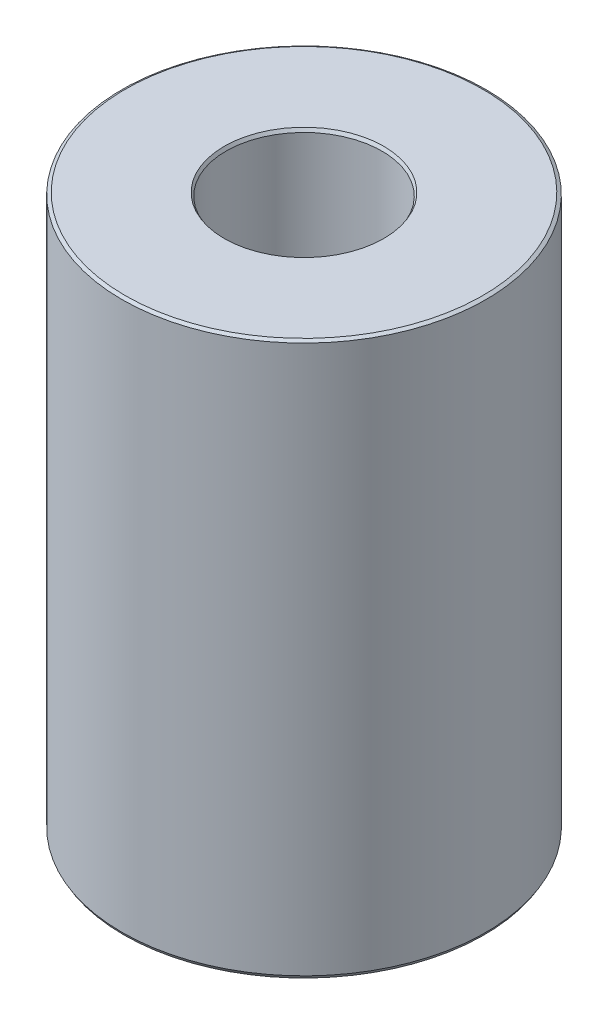
SolidWorks part; units mm, degrees
ref_plane "Front Plane" through (0, 0, 0) normal (0, 0, 1) x (1, 0, 0)
ref_plane "Top Plane" through (0, 0, 0) normal (0, 1, 0) x (1, 0, 0)
ref_plane "Right Plane" through (0, 0, 0) normal (1, 0, 0) x (0, 0, -1)
sketch "Sketch1" plane through (0, 0, 0) normal (0, 1, 0) x (1, 0, 0)
  circle A0 centre (0, 0) radius 55
  dimension "SLEEVE_OD" = 110
extrude "Boss-Extrude1" add sketch "Sketch1" along normal blind 167.1631
sketch "Sketch2" plane through (0, 0, 0) normal (0, 1, 0) x (1, 0, 0)
  circle A0 centre (0, 0) radius 23.5777
  dimension "BORE_D" = 47.1554
extrude "Cut-Extrude1" cut sketch "Sketch2" along normal through all
chamfer "Chamfer1" distance 0.5573 angle 60 4 edges at (0, 167.1631, 23.5777) (0, 0, 23.5777) (0, 0, 55) (0, 167.1631, 55) first distance on face at (0, 167.1631, 23.5777) first distance on face at (0, 0, 23.5777) first distance on face at (0, 167.1631, 55)
